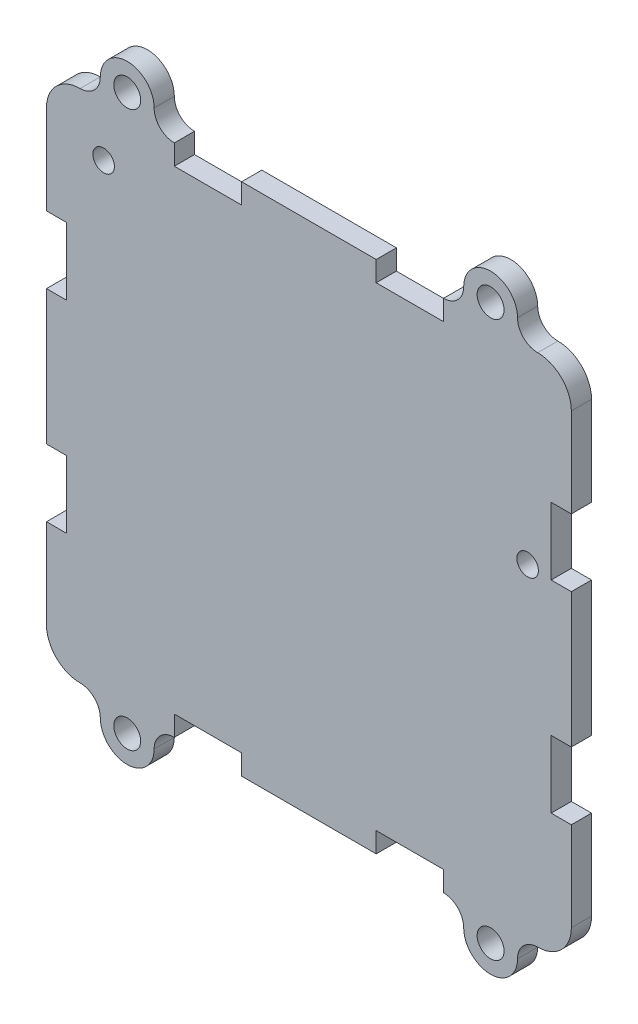
SolidWorks part; units mm, degrees
ref_plane "Front Plane" through (0, 0, 0) normal (0, 0, 1) x (1, 0, 0)
ref_plane "Top Plane" through (0, 0, 0) normal (0, 1, 0) x (1, 0, 0)
ref_plane "Right Plane" through (0, 0, 0) normal (1, 0, 0) x (0, 0, -1)
sketch "Sketch1" plane through (0, 0, 0) normal (0, 0, 1) x (1, 0, 0)
  line L12 (52, -29) -> (52, 47.5)
  line L13 (52, 47.5) -> (-26, 47.5)
  line L14 (-26, -29) -> (52, -29)
  line L15 (-26, 47.5) -> (-26, -29)
  line L16 (52, -24) -> (52, 42.5)
  line L17 (47, 47.5) -> (-21, 47.5)
  line L18 (-21, -29) -> (47, -29)
  line L19 (-26, 42.5) -> (-26, -24)
  arc A10 (-21, -29) -> (-26, -24) centre (-21, -24) cw
  arc A11 (52, -24) -> (47, -29) centre (47, -24) cw
  arc A12 (52, 42.5) -> (47, 47.5) centre (47, 42.5) ccw
  arc A13 (-21, 47.5) -> (-26, 42.5) centre (-21, 42.5) ccw
  dimension "D2" = 5
  dimension "D1" = 3
extrude "Boss-Extrude1" add sketch "Sketch1" along normal blind 3 contours L19 A10 L18 A11 L16 A12 L17 A13
sketch "Sketch3" plane through (0, 0, 0) normal (0, 0, -1) x (-1, 0, 0)
  circle A0 centre (17.5, 40) radius 1.6
  circle A1 centre (-45.5, 19.5) radius 1.6
extrude "Cut-Extrude1" cut sketch "Sketch3" against normal blind 3
sketch "Sketch4" plane through (0, 0, 0) normal (0, 0, -1) x (-1, 0, 0)
  line L0 (26, 9.25) -> (-52, 9.25) construction
  line L1 (26, 42.5) -> (26, -24) construction
  line L2 (-52, -24) -> (-52, 42.5) construction
  line L3 (26, -10.75) -> (23, -0.75) construction
  line L4 (21, -29) -> (-47, -29) construction
  line L5 (-13, -29) -> (-13, 47.5) construction
  line L6 (-47, 47.5) -> (21, 47.5) construction
  line L7 (26, 19.25) -> (23, 19.25)
  line L8 (26, 19.25) -> (26, 29.25)
  line L9 (26, 29.25) -> (23, 29.25)
  line L10 (23, 19.25) -> (23, 29.25)
  line L11 (26, 19.25) -> (23, 29.25) construction
  line L12 (26, 29.25) -> (23, 19.25) construction
  line L13 (26, -0.75) -> (23, -10.75) construction
  line L14 (23, -0.75) -> (23, -10.75)
  line L15 (26, -10.75) -> (23, -10.75)
  line L16 (26, -0.75) -> (26, -10.75)
  line L17 (26, -0.75) -> (23, -0.75)
  line L18 (-52, -0.75) -> (-49, -10.75) construction
  line L19 (-52, 29.25) -> (-49, 19.25) construction
  line L20 (-52, 19.25) -> (-49, 29.25) construction
  line L21 (-52, -10.75) -> (-49, -0.75) construction
  line L22 (-52, -0.75) -> (-49, -0.75)
  line L23 (-52, -0.75) -> (-52, -10.75)
  line L24 (-52, -10.75) -> (-49, -10.75)
  line L25 (-49, -0.75) -> (-49, -10.75)
  line L26 (-49, 19.25) -> (-49, 29.25)
  line L27 (-52, 29.25) -> (-49, 29.25)
  line L28 (-52, 19.25) -> (-52, 29.25)
  line L29 (-52, 19.25) -> (-49, 19.25)
  line L30 (-33, 44.5) -> (-23, 47.5) construction
  line L31 (7, 47.5) -> (-3, 47.5)
  line L32 (7, 47.5) -> (7, 44.5)
  line L33 (7, 44.5) -> (-3, 44.5)
  line L34 (-3, 47.5) -> (-3, 44.5)
  line L35 (7, 47.5) -> (-3, 44.5) construction
  line L36 (7, 44.5) -> (-3, 47.5) construction
  line L37 (-33, 47.5) -> (-23, 44.5) construction
  line L38 (-23, 47.5) -> (-23, 44.5)
  line L39 (-33, 44.5) -> (-23, 44.5)
  line L40 (-33, 47.5) -> (-33, 44.5)
  line L41 (-33, 47.5) -> (-23, 47.5)
  line L42 (-33, -29) -> (-23, -26) construction
  line L43 (7, -26) -> (-3, -29) construction
  line L44 (7, -29) -> (-3, -26) construction
  line L45 (-33, -26) -> (-23, -29) construction
  line L46 (-33, -29) -> (-23, -29)
  line L47 (-33, -29) -> (-33, -26)
  line L48 (-33, -26) -> (-23, -26)
  line L49 (-23, -29) -> (-23, -26)
  line L50 (-3, -29) -> (-3, -26)
  line L51 (7, -26) -> (-3, -26)
  line L52 (7, -29) -> (7, -26)
  line L53 (7, -29) -> (-3, -29)
  point P16 (24.5, 24.25)
  point P21 (24.5, -5.75)
  point P30 (-50.5, -5.75)
  point P31 (-50.5, 24.25)
  point P36 (2, 46)
  point P41 (-28, 46)
  point P50 (-28, -27.5)
  point P51 (2, -27.5)
  dimension "D1" = 3
  dimension "D2" = 10
  dimension "D3" = 10
  dimension "D4" = 10
  dimension "D5" = 3
  dimension "D6" = 10
extrude "Cut-Extrude2" cut sketch "Sketch4" against normal blind 3
sketch "Sketch5" plane through (0, 0, 3) normal (0, 0, 1) x (1, 0, 0)
  line L0 (-7, 47.5) -> (-21, 47.5) construction
  line L1 (-18, 47.5) -> (-10, 47.5)
  line L2 (-18, 47.5) -> (-18, 50.5)
  line L4 (-10, 47.5) -> (-10, 50.5)
  line L5 (-18, 47.5) -> (-10, 53.5) construction
  line L6 (-18.1906, 53.6429) -> (-10, 47.5) construction
  line L7 (-14, 54.5) -> (-14, 47.5) construction
  line L8 (13, 47.5) -> (13, -29) construction
  line L9 (23, 47.5) -> (3, 47.5) construction
  line L10 (3, -29) -> (23, -29) construction
  line L11 (40, 54.5) -> (40, 47.5) construction
  line L12 (44.1906, 53.6429) -> (36, 47.5) construction
  line L13 (44, 47.5) -> (36, 53.5) construction
  line L14 (36, 47.5) -> (36, 50.5)
  line L15 (44, 47.5) -> (44, 50.5)
  line L16 (44, 47.5) -> (36, 47.5)
  line L17 (-26, 9.25) -> (52, 9.25) construction
  line L18 (-26, 19.25) -> (-26, -0.75) construction
  line L19 (52, -0.75) -> (52, 19.25) construction
  line L20 (44, -29) -> (36, -35) construction
  line L21 (44.1906, -35.1429) -> (36, -29) construction
  line L22 (40, -36) -> (40, -29) construction
  line L23 (44, -29) -> (36, -29)
  line L24 (44, -29) -> (44, -32)
  line L25 (36, -29) -> (36, -32)
  line L26 (-14, -36) -> (-14, -29) construction
  line L27 (-18.1906, -35.1429) -> (-10, -29) construction
  line L28 (-18, -29) -> (-10, -35) construction
  line L29 (-10, -29) -> (-10, -32)
  line L30 (-18, -29) -> (-18, -32)
  line L31 (-18, -29) -> (-10, -29)
  arc A0 (-10, 50.5) -> (-18, 50.5) centre (-14, 50.5) ccw
  circle A1 centre (-14, 50.5) radius 2
  circle A2 centre (40, 50.5) radius 2
  arc A3 (36, 50.5) -> (44, 50.5) centre (40, 50.5) cw
  arc A4 (36, -32) -> (44, -32) centre (40, -32) ccw
  circle A5 centre (40, -32) radius 2
  circle A6 centre (-14, -32) radius 2
  arc A7 (-10, -32) -> (-18, -32) centre (-14, -32) cw
  dimension "D1" = 4
  dimension "D2" = 4
  dimension "D3" = 3
extrude "Boss-Extrude2" add sketch "Sketch5" against normal blind 3
fillet "Fillet1" radius 3 8 edges at (-10, 47.5, 1.5) (-18, 47.5, 1.5) (36, 47.5, 1.5) (44, 47.5, 1.5) (44, -29, 1.5) (36, -29, 1.5) (-10, -29, 1.5) (-18, -29, 1.5)
